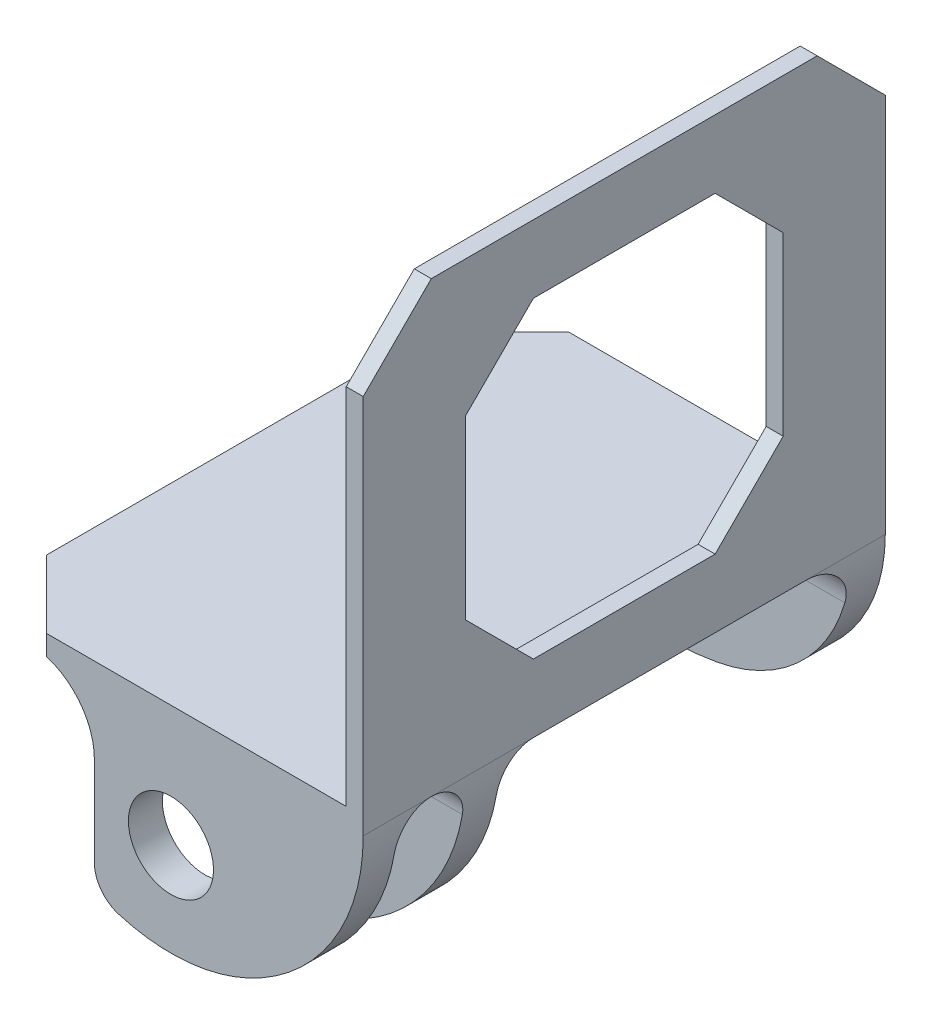
SolidWorks part; units mm, degrees
material "ABS PC"
ref_plane "Front Plane" through (0, 0, 0) normal (0, 0, 1) x (1, 0, 0)
ref_plane "Top Plane" through (0, 0, 0) normal (0, 1, 0) x (1, 0, 0)
ref_plane "Right Plane" through (0, 0, 0) normal (1, 0, 0) x (0, 0, -1)
sketch "Sketch1" plane through (0, 0, 0) normal (0, 1, 0) x (1, 0, 0)
  line L0 (0, 48.7045) -> (71.755, 48.7045) construction
  line L1 (0, 0) -> (71.755, 0)
  line L2 (0, 0) -> (0, 97.409)
  line L3 (0, 97.409) -> (71.755, 97.409)
  line L4 (71.755, 0) -> (71.755, 97.409)
  line L5 (35.8775, 97.409) -> (35.8775, 0) construction
  dimension "D1" = 71.755
  dimension "D2" = 97.409
extrude "Boss-Extrude1" add sketch "Sketch1" along normal blind 3.175
ref_plane "Plane2" through (0, 0, -48.7045) normal (0, 0, -1) x (-1, 0, 0)
ref_plane "Plane1" through (35.8775, 0, 0) normal (1, 0, 0) x (0, 0, -1)
sketch "Sketch3" plane through (0, 3.175, 0) normal (0, 1, 0) x (1, 0, 0)
  line L0 (71.755, 0) -> (68.58, 0)
  line L1 (0, 0) -> (71.755, 0) construction
  line L2 (68.58, 0) -> (68.58, 97.409)
  line L3 (71.755, 97.409) -> (0, 97.409) construction
  line L4 (68.58, 97.409) -> (71.755, 97.409)
  line L5 (71.755, 97.409) -> (71.755, 0)
  dimension "D1" = 3.175
extrude "Boss-Extrude4" add sketch "Sketch3" along normal blind 80.518
sketch "Sketch8" plane through (0, 0, -48.7045) normal (0, 0, 1) x (1, 0, 0)
  line L0 (25.0825, 0) -> (25.0825, -29.972)
  line L1 (0, 0) -> (71.755, 0) construction
  line L2 (46.6725, 0) -> (46.6725, -29.972) construction
  line L3 (46.6725, -29.972) -> (25.0825, -29.972) construction
  line L4 (25.0825, 0) -> (46.6725, 0)
  line L5 (35.8775, -46.0311) -> (35.8775, 46.0311) construction
  line L6 (46.6725, 0) -> (71.755, 0)
  circle A1 centre (35.8775, -19.472) radius 3.175
  arc A4 (71.755, 0) -> (46.6725, -29.972) centre (41.3064, 0) cw
  arc A5 (46.6725, -29.972) -> (25.0825, -29.972) centre (35.8775, 30.3231) cw
  point P8 (35.8775, 0)
  dimension "D3" = 10.5
  dimension "D4" = 6.35
  dimension "D1" = 21.59
  dimension "D2" = 29.972
extrude "Boss-Extrude10" add sketch "Sketch8" along normal blind 6.35 from surface at -48.7045 contours L4 L6 A4 A5 L0 | A1 starting at face at (46.7783, 28.956, -97.409)
sketch "Sketch9" plane through (71.755, 0, 0) normal (1, 0, 0) x (0, 0, -1)
  line L0 (0, 83.693) -> (97.409, 0) construction
  line L1 (97.409, 83.693) -> (97.409, 0) construction
  line L2 (19.05, 12.7) -> (78.359, 12.7)
  line L3 (19.05, 12.7) -> (19.05, 70.993)
  line L4 (19.05, 70.993) -> (78.359, 70.993)
  line L5 (78.359, 12.7) -> (78.359, 70.993)
  line L6 (19.05, 12.7) -> (78.359, 70.993) construction
  line L7 (19.05, 70.993) -> (78.359, 12.7) construction
  line L8 (0, 83.693) -> (97.409, 83.693) construction
  point P4 (48.7045, 41.8465)
  dimension "D1" = 19.05
  dimension "D2" = 12.7
extrude "Cut-Extrude1" cut sketch "Sketch9" against normal up to next contours L3 L2 L5 L4
fillet "Fillet3" radius 12.7 4 edges at (70.1675, 83.693, 0) (0, 1.5875, 0) (70.1675, 83.693, -97.409) (0, 1.5875, -97.409) profile chamfer
chamfer "Chamfer1" distance 12.7 angle 45 4 edges at (70.1675, 12.7, -19.05) (70.1675, 12.7, -78.359) (70.1675, 70.993, -78.359) (70.1675, 70.993, -19.05)
sketch "Sketch10" plane through (0, 0, 0) normal (0, 0, 1) x (1, 0, 0)
  line L0 (35.8775, -19.472) -> (35.8775, 0)
  line L1 (50.165, 0) -> (71.755, 0)
  line L2 (21.59, 0) -> (21.59, -33.7595)
  line L3 (12.7, 0) -> (71.755, 0) construction
  line L4 (21.59, -33.7595) -> (50.165, -33.7595) construction
  line L5 (50.165, -33.7595) -> (50.165, 0) construction
  line L6 (21.59, 0) -> (50.165, 0)
  circle A0 centre (35.8775, -19.472) radius 7.9375
  arc A2 (71.755, 0) -> (50.165, -33.7595) centre (34.5657, 0) cw
  arc A3 (50.165, -33.7595) -> (21.59, -33.7595) centre (35.8775, -2.8389) cw
  dimension "D1" = 15.875
  dimension "D2" = 14.2875
  dimension "D3" = 28.575
  dimension "D4" = 14.2875
extrude "Boss-Extrude11" add sketch "Sketch10" against normal blind 6.35 from surface at 0
pattern_linear "LPattern1" count 2 spacing 19.05 along (0, 0, -1) of "Boss-Extrude11"
fillet "Fillet2" radius 8.4667 1 edges at (48.4187, 0, -91.059)
fillet "Fillet4" radius 6.35 6 edges at (46.6725, 0, -6.35) (46.6725, 0, -25.4) (46.6725, 0, -19.05) (21.59, -33.7595, -3.175) (21.59, -33.7595, -22.225) (25.0825, -29.972, -94.234)
fillet "Fillet5" radius 12.7 3 edges at (21.59, 0, -6.35) (21.59, 0, -22.225) (25.0825, 0, -90.0007)
